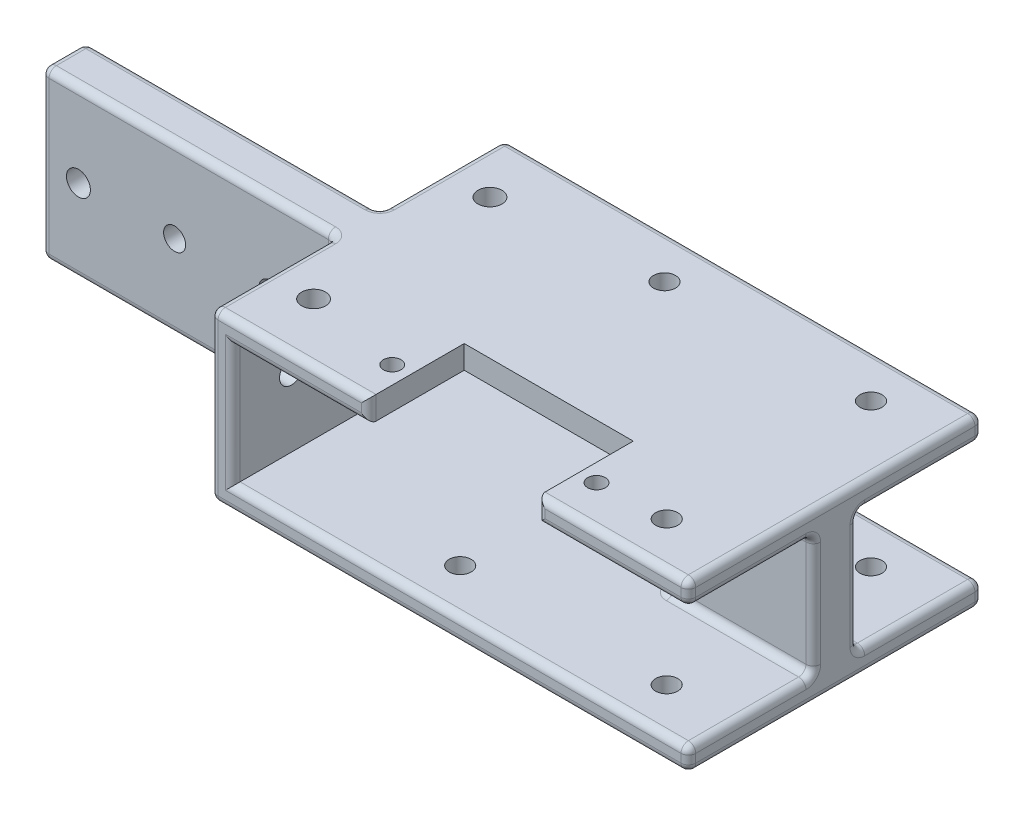
SolidWorks part; units mm, degrees
note: The reader was unsure of these and kept them because the rebuilt part matched: shared geometry of "Sketch1<2>".
material "Delrin 2700 NC010, Low Viscosity Acetal Copolymer (SS)"
ref_plane "Front Plane" through (0, 0, 0) normal (0, 0, 1) x (1, 0, 0)
ref_plane "Top Plane" through (0, 0, 0) normal (0, 1, 0) x (1, 0, 0)
ref_plane "Right Plane" through (0, 0, 0) normal (1, 0, 0) x (0, 0, -1)
sketch "Sketch1" plane through (0, 0, 0) normal (0, 1, 0) x (1, 0, 0)
  line L1 (0, 20) -> (65, 20)
  line L2 (0, 20) -> (0, -20)
  line L3 (0, -20) -> (65, -20)
  line L4 (65, 20) -> (65, -20)
  point P4 (0, 0)
  dimension "D1" = 65
  dimension "D2" = 40
extrude "Boss-Extrude1" add sketch "Sketch1" against normal blind 3.15
extrude "Boss-Extrude2" add sketch "Sketch1<2>" along normal blind 3.15 from offset 16.4 separate body
sketch "Sketch1<2>" plane through (0, 0, 0) normal (0, 1, 0) x (1, 0, 0) same geometry as "Sketch1"
sketch "Sketch2" plane through (0, 0, 0) normal (0, 1, 0) x (1, 0, 0)
  line L0 (0, -20) -> (65, -20) construction
  line L1 (0, 20) -> (3, 20)
  line L2 (0, 20) -> (0, -20)
  line L3 (0, -20) -> (3, -20)
  line L4 (3, 20) -> (3, -20)
  line L5 (65, -20) -> (65, 20) construction
  line L6 (65, 3) -> (45, 3)
  line L7 (65, 3) -> (65, -3)
  line L8 (65, -3) -> (45, -3)
  line L9 (45, 3) -> (45, -3)
  point P14 (65, 0)
  dimension "D2" = 6
  dimension "D3" = 20
extrude "Boss-Extrude3" add sketch "Sketch2" along normal up to surface (16.4 mm away) up to face at (32.5, 16.4, 0)
sketch "Sketch3" plane through (0, 0, 0) normal (-1, 0, 0) x (0, 0, 1)
  line L0 (-20, 19.55) -> (20, 19.55) construction
  line L1 (-3, 19.55) -> (3, 19.55)
  line L2 (-3, 19.55) -> (-3, -3.15)
  line L3 (-3, -3.15) -> (3, -3.15)
  line L4 (3, 19.55) -> (3, -3.15)
  line L5 (-20, -3.15) -> (20, -3.15) construction
  point P8 (0, 19.55)
  dimension "D3" = 6
extrude "Boss-Extrude4" add sketch "Sketch3" along normal blind 40
hole_wizard "M2 Clearance Hole1" positions "Sketch7" profile "Sketch9" hole size "M2" standard "ANSI Metric"
sketch "Sketch7" plane through (0, 19.55, 0) normal (0, 1, 0) x (1, 0, 0)
  line L1 (0, -20) -> (65, -20) construction
  line L2 (65, -20) -> (65, 20) construction
  point P0 (19.1, -14.4)
  point P2 (46.9, -14.4)
  point P5 (19.1, -14.4)
  point P7 (46.9, -14.4)
  dimension "D1" = 27.8
  dimension "D3" = 5.6
  dimension "D2" = 18.1
sketch "Sketch9" plane through (19.1, 19.55, 14.4) normal (1, 0, 0) x (0, 0, 1)
  line L0 (0, 0) -> (0, 5.721)
  line L1 (0, 5.721) -> (1.2, 5)
  line L2 (1.2, 5) -> (1.2, 0)
  line L5 (1.2, 0) -> (0, 0)
  line L10 (0, 5.721) -> (-1.2, 5) construction
  line L11 (0, -6.35) -> (0, 107.95) construction
  dimension "Hole Dia." = 2.4
  dimension "Hole Depth" = 5
  dimension "Drill Angle" = 118
hole_wizard "Ø3.0mm Dowel Hole1" positions "Sketch10" profile "Sketch11" hole size "Ø3.0" standard "ANSI Metric" end condition through all
sketch "Sketch10" plane through (0, 19.55, 0) normal (0, 1, 0) x (1, 0, 0)
  line L0 (0, -20) -> (65, -20) construction
  line L1 (65, -20) -> (65, 20) construction
  point P0 (55.95, -13.9)
  point P7 (27.85, 13.9)
  point P13 (55.95, 13.9)
  point P14 (27.85, -13.9)
  dimension "D1" = 6.1
  dimension "D2" = 9.05
  dimension "D4" = 37.15
  dimension "D3" = 27.8
sketch "Sketch11" plane through (55.95, 19.55, 13.9) normal (1, 0, 0) x (0, 0, 1)
  line L0 (0, 0) -> (0, 22.7)
  line L1 (0, 22.7) -> (1.5, 22.7)
  line L2 (1.5, 22.7) -> (1.5, 0)
  line L5 (1.5, 0) -> (0, 0)
  line L11 (0, -6.35) -> (0, 107.95) construction
  dimension "Thru Hole Dia." = 3
  dimension "Thru Hole Depth" = 22.7
sketch "Sketch5" plane through (0, 19.55, 0) normal (0, 1, 0) x (1, 0, 0)
  line L0 (0, -20) -> (65, -20) construction
  line L1 (21.5, -20) -> (44.5, -20)
  line L2 (21.5, -20) -> (21.5, -7)
  line L3 (21.5, -7) -> (44.5, -7)
  line L4 (44.5, -20) -> (44.5, -7)
  circle A0 centre (46.9, -14.4) radius 1.2 construction
  point P6 (33, -7)
  dimension "D1" = 23
  dimension "D2" = 13.9
  dimension "D3" = 13
extrude "Cut-Extrude1" cut sketch "Sketch5" against normal blind 7
fillet "Fillet1" radius 1 50 edges at (65, -3.15, 0) (54.75, 19.55, 20) (54.75, 16.4, 20) (21.5, 17.975, 20) (44.5, 17.975, 20) (32.5, -3.15, -20) (34, 0, 20) (3, 8.2, 20) (3, 8.2, -20) (12.25, 16.4, 20) (65, 16.4, 11.5) (65, 17.975, 20) (34, 16.4, -20) (65, 17.975, -20) (0, 19.55, -11.5) (10.75, 19.55, 20) (65, 19.55, 0) (32.5, 19.55, -20) (65, 16.4, -11.5) (65, 0, -11.5) (65, 8.2, 3) (65, 8.2, -3) (55, 0, -3) (45, 8.2, -3) (45, 0, 0) (45, 8.2, 3) (55, 0, 3) (55, 16.4, 3) (55, 16.4, -3) (45, 16.4, 0) (0, -3.15, -11.5) (34, 0, -20) (0, 19.55, 11.5) (0, -3.15, 11.5) (65, 0, 11.5) (0, 8.2, -3) (-20, 19.55, -3) (-20, -3.15, -3) (0, 8.2, 3) (-20, -3.15, 3) (-20, 19.55, 3) (-40, 8.2, -3) (-40, -3.15, 0) (-40, 8.2, 3) (-40, 19.55, 0) (32.5, -3.15, 20) (0, 8.2, -20) (65, -1.575, -20) (65, -1.575, 20) (0, 8.2, 20)
hole_wizard "#4 Clearance Hole1" positions "Sketch14" profile "Sketch15" hole size "#4" standard "ANSI Inch" end condition through all
sketch "Sketch14" plane through (0, 0, 3) normal (0, 0, 1) x (1, 0, 0)
  line L0 (-40, -2.15) -> (-40, 18.55) construction
  point P0 (-35, 8.2)
  point P2 (-8.82, 8.2)
  point P7 (-40, 8.2)
  dimension "D1" = 26.18
  dimension "D2" = 5
sketch "Sketch15" plane through (-35, 8.2, 3) normal (1, 0, 0) x (0, -1, 0)
  line L0 (0, 0) -> (0, 23)
  line L1 (0, 23) -> (1.6319, 23)
  line L2 (1.6319, 23) -> (1.6319, 0)
  line L5 (1.6319, 0) -> (0, 0)
  line L11 (0, -6.35) -> (0, 107.95) construction
  dimension "Thru Hole Dia." = 3.2639
  dimension "Thru Hole Depth" = 23
hole_wizard "Ø3.0mm Dowel Hole2" positions "Sketch16" profile "Sketch17" hole size "Ø3.0" standard "ANSI Metric" end condition through all
sketch "Sketch16" plane through (0, 0, 3) normal (0, 0, 1) x (1, 0, 0)
  line L0 (-40, -2.15) -> (-40, 18.55) construction
  circle A0 centre (-35, 8.2) radius 1.632 construction
  point P0 (-21.91, 8.2)
  point P8 (-40, 8.2)
  dimension "D1" = 13.09
sketch "Sketch17" plane through (-21.91, 8.2, 3) normal (1, 0, 0) x (0, -1, 0)
  line L0 (0, 0) -> (0, 23)
  line L1 (0, 23) -> (1.5, 23)
  line L2 (1.5, 23) -> (1.5, 0)
  line L5 (1.5, 0) -> (0, 0)
  line L11 (0, -6.35) -> (0, 107.95) construction
  dimension "Thru Hole Dia." = 3
  dimension "Thru Hole Depth" = 23
hole_wizard "#4 Clearance Hole2" positions "Sketch18" profile "Sketch19" hole size "#4" standard "ANSI Inch"
sketch "Sketch18" plane through (0, 19.55, 0) normal (0, 1, 0) x (1, 0, 0)
  point P0 (6, 12)
  point P2 (6, -12)
  dimension "D1" = 12
  dimension "D2" = 12
  dimension "D3" = 6
sketch "Sketch19" plane through (6, 19.55, -12) normal (1, 0, 0) x (0, 0, 1)
  line L0 (0, 0) -> (0, 10.9806)
  line L1 (0, 10.9806) -> (1.6319, 10)
  line L2 (1.6319, 10) -> (1.6319, 0)
  line L5 (1.6319, 0) -> (0, 0)
  line L10 (0, 10.9806) -> (-1.632, 10) construction
  line L11 (0, -6.35) -> (0, 107.95) construction
  dimension "Hole Dia." = 3.2639
  dimension "Hole Depth" = 10
  dimension "Drill Angle" = 118
hole_wizard "#4 Clearance Hole3" positions "Sketch20" profile "Sketch21" hole size "#4" standard "ANSI Inch" end condition through all
sketch "Sketch20" plane through (0, 0, 0) normal (-1, 0, 0) x (0, 0, 1)
  line L0 (4, 19.55) -> (19, 19.55) construction
  point P0 (-12, 9.55)
  point P2 (12, 9.55)
  dimension "D2" = 12
  dimension "D1" = 10
  dimension "D3" = 12
sketch "Sketch21" plane through (0, 9.55, -12) normal (0, 1, 0) x (0, 0, 1)
  line L0 (0, 0) -> (0, 65)
  line L1 (0, 65) -> (1.6319, 65)
  line L2 (1.6319, 65) -> (1.6319, 0)
  line L5 (1.6319, 0) -> (0, 0)
  line L11 (0, -6.35) -> (0, 107.95) construction
  dimension "Thru Hole Dia." = 3.2639
  dimension "Thru Hole Depth" = 65
equation "\"D2@Sketch7\"=9.05*2"
equation "\"D1@Sketch10\"=(40-\"D3@Sketch10\")/2"
equation "\"D3@Sketch7\"=5.6"
equation "\"D2@Sketch18\"=\"D1@Sketch18\""
equation "\"D3@Sketch20\"=\"D2@Sketch20\""
